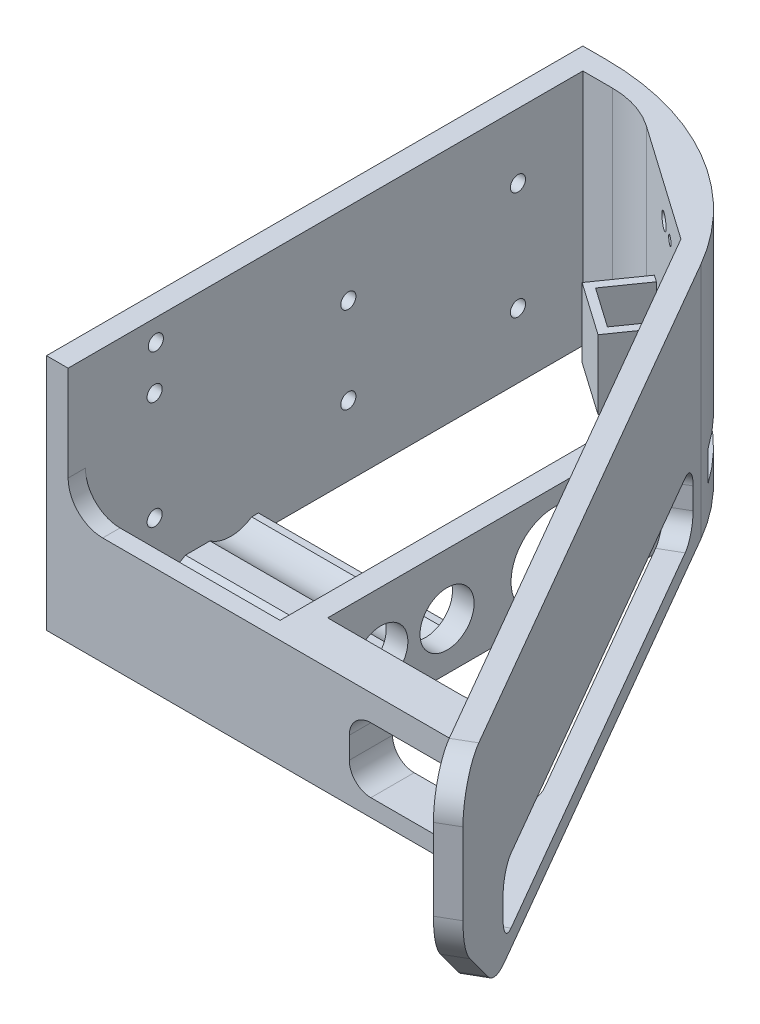
SolidWorks part; units mm, degrees
ref_plane "Front" through (0, 0, 0) normal (0, 0, 1) x (1, 0, 0)
ref_plane "Top" through (0, 0, 0) normal (0, 1, 0) x (1, 0, 0)
ref_plane "Right" through (0, 0, 0) normal (1, 0, 0) x (0, 0, -1)
sketch "Sketch3" plane through (0, 0, 0) normal (0, 1, 0) x (1, 0, 0)
  line L0 (128.1699, -162.7147) -> (55, -35.9808)
  line L1 (0, 0) -> (40, 0)
  line L2 (0, 0) -> (0, -124)
  line L3 (0, -124) -> (5, -124)
  line L4 (5, -5) -> (5, -124)
  line L5 (40, 0) -> (132.5, -160.2147)
  line L6 (132.5, -160.2147) -> (128.1699, -162.7147)
  line L7 (5, -5) -> (18.123, -5)
  line L10 (50, -27.3205) -> (50, -124)
  line L11 (50, -124) -> (55, -124)
  line L12 (55, -35.9808) -> (55, -124)
  line L13 (18.123, -5) -> (50, -27.3205)
  dimension "D1" = 5
  dimension "D2" = 5
  dimension "D3" = 5
  dimension "D4" = 120
  dimension "D5" = 124
  dimension "D6" = 185
  dimension "D7" = 40
  dimension "D8" = 5
  dimension "D9" = 45
  dimension "D10" = 145
extrude "Boss-Extrude3" add sketch "Sketch3" along normal blind 55 contours L2 L3 L4 L7 L13 L10 L11 L12 L0 L6 L5 L1
fillet "Fillet1" radius 60 1 edges at (40, 27.5, 0)
sketch "Sketch4" plane through (3.6131, 0, -5.16) normal (-0.5736, 0, 0.8192) x (0.8192, 0, 0.5736)
  line L1 (31.628, 30.3662) -> (46.628, 30.3662)
  line L2 (31.628, 30.3662) -> (31.628, 14.3662)
  line L3 (31.628, 14.3662) -> (46.628, 14.3662)
  line L4 (46.628, 30.3662) -> (46.628, 14.3662)
  line L5 (56.628, 55) -> (56.628, 0) construction
  dimension "D1" = 15
  dimension "D2" = 16
  dimension "D3" = 10
extrude "Boss-Extrude4" add sketch "Sketch4" along normal blind 12
sketch "Sketch5" plane through (3.6131, 0, -5.16) normal (-0.5736, 0, 0.8192) x (0.8192, 0, 0.5736)
  line L1 (19.128, 14.3662) -> (59.128, 14.3662)
  line L2 (19.128, 14.3662) -> (19.128, 7.3662)
  line L3 (19.128, 7.3662) -> (59.128, 7.3662)
  line L4 (59.128, 14.3662) -> (59.128, 7.3662)
  line L5 (39.128, 14.3662) -> (39.128, -8.9782) construction
  line L6 (31.628, 14.3662) -> (46.628, 14.3662) construction
  dimension "D1" = 40
  dimension "D2" = 7
extrude "Cut-Extrude1" cut sketch "Sketch5" against normal blind 14 and the other way blind 20
sketch "Sketch6" plane through (0, 30.3662, 0) normal (0, 1, 0) x (1, 0, 0)
  line L0 (31.0776, -14.0709) -> (25.2845, -22.3443)
  line L1 (25.2845, -22.3443) -> (34.459, -28.7684)
  line L2 (34.459, -28.7684) -> (40.2521, -20.4949)
  line L3 (40.2521, -20.4949) -> (31.0776, -14.0709)
  line L4 (34.9256, -31.4146) -> (41.8085, -21.5847) construction
  line L5 (22.6383, -22.8109) -> (29.5212, -12.9811) construction
  line L6 (34.9256, -31.4146) -> (22.6383, -22.8109) construction
  line L7 (41.8085, -21.5847) -> (29.5212, -12.9811) construction
  dimension "D1" = 1.9
  dimension "D2" = 1.9
  dimension "D3" = 1.9
extrude "Cut-Extrude2" cut sketch "Sketch6" against normal offset from surface (14 mm away) 2 up to face at (36.2555, 14.3662, 19.8332)
sketch "Sketch7" plane through (0, 16.3662, 0) normal (0, 1, 0) x (1, 0, 0)
  line L0 (31.0776, -14.0709) -> (34.459, -28.7684) construction
  line L1 (34.459, -28.7684) -> (25.2845, -22.3443) construction
  circle A0 centre (32.7683, -21.4196) radius 2
  dimension "D1" = 4
extrude "Cut-Extrude3" cut sketch "Sketch7" against normal blind 2
sketch "Sketch8" plane through (0, 55, 0) normal (0, 1, 0) x (1, 0, 0)
  line L0 (55, -35.9808) -> (50, -27.3205)
  line L1 (50, -27.3205) -> (50, -124)
  line L2 (50, -124) -> (55, -124)
  line L3 (55, -124) -> (55, -35.9808)
extrude "Cut-Extrude4" cut sketch "Sketch8" against normal blind 30
sketch "Sketch9" plane through (50, 0, 0) normal (-1, 0, 0) x (0, 0, 1)
  line L0 (27.3205, 0) -> (124, 0) construction
  circle A0 centre (61.5987, 11) radius 10
  circle A1 centre (86.3851, 11) radius 6.25
  circle A2 centre (101.7, 11) radius 6.25
  dimension "D1" = 12.5
  dimension "D2" = 12.5
  dimension "D3" = 20
  dimension "D4" = 11
extrude "Cut-Extrude5" cut sketch "Sketch9" against normal up to surface (5 mm away) up to face at (55, 12.5, 79.9904)
sketch "Sketch10" plane through (30, 0, -17.3205) normal (0.866, 0, -0.5) x (-0.5, 0, -0.866)
  line L0 (-54.641, 0) -> (-205, 0) construction
  line L1 (-179.641, 4) -> (-59.641, 4)
  line L2 (-179.641, 4) -> (-179.641, 19)
  line L3 (-179.641, 19) -> (-59.641, 19)
  line L4 (-59.641, 4) -> (-59.641, 19)
  line L5 (-54.641, 0) -> (-54.641, 55) construction
  dimension "D1" = 15
  dimension "D2" = 4
  dimension "D3" = 120
  dimension "D4" = 5
extrude "Cut-Extrude6" cut sketch "Sketch10" against normal up to surface (5 mm away) up to face at (77.7233, 26.6667, 75.3387)
sketch "Sketch11" plane through (50, 0, 0) normal (-1, 0, 0) x (0, 0, 1)
  line L0 (27.3205, 0) -> (124, 0) construction
  line L1 (124, 25) -> (120, 25)
  line L2 (124, 25) -> (124, 0)
  line L3 (124, 0) -> (120, 0)
  line L4 (120, 25) -> (120, 0)
  dimension "D1" = 4
extrude "Boss-Extrude5" add sketch "Sketch11" along normal up to surface (45 mm away) up to face at (5, 27.5, 64.5)
fillet "Fillet3" radius 20 1 edges at (18.123, 27.5, 5)
sketch "Sketch12" plane through (55, 0, 0) normal (1, 0, 0) x (0, 0, -1)
  line L1 (-124, 0) -> (-114, 0)
  line L2 (-124, 0) -> (-124, 4)
  line L3 (-124, 4) -> (-114, 4)
  line L4 (-114, 0) -> (-114, 4)
  dimension "D1" = 10
  dimension "D2" = 4
extrude "Boss-Extrude6" add sketch "Sketch12" along normal up to surface (50.8179 mm away) up to face at (85.4904, 11.5, 88.7917)
sketch "Sketch13" plane through (50, 0, 0) normal (-1, 0, 0) x (0, 0, 1)
  line L1 (80, 0) -> (120, 0)
  line L2 (80, 0) -> (80, 4)
  line L3 (80, 4) -> (120, 4)
  line L4 (120, 0) -> (120, 4)
  line L5 (120, 25) -> (120, 0) construction
  dimension "D1" = 4
  dimension "D2" = 40
extrude "Boss-Extrude7" add sketch "Sketch13" along normal up to surface (45 mm away) up to face at (5, 26.6667, 83)
fillet "Fillet4" radius 5 4 edges at (57.6554, 4, 35.5801) (117.6554, 4, 139.5032) (117.6554, 19, 139.5032) (57.6554, 19, 35.5801)
sketch "Sketch14" plane through (50, 0, 0) normal (-1, 0, 0) x (0, 0, 1)
  arc A0 (94.0426, 14.6896) -> (94.0426, 7.3104) centre (86.3851, 11) ccw
  arc A1 (94.0426, 7.3104) -> (94.0426, 14.6896) centre (101.7, 11) ccw
  circle A2 centre (101.7, 11) radius 6.25 construction
  circle A3 centre (86.3851, 11) radius 6.25 construction
  dimension "D1" = 17
  dimension "D2" = 17
extrude "Cut-Extrude7" cut sketch "Sketch14" along normal up to surface (45 mm away) up to face at (5, 21, 82.25)
sketch "Sketch15" plane through (0, 0, 0) normal (-1, 0, 0) x (0, 0, 1)
  line L0 (0, 55) -> (124, 55) construction
  line L1 (0, 55) -> (0, 0) construction
  line L2 (0, 0) -> (124, 0) construction
  line L3 (124, 55) -> (124, 0) construction
  circle A0 centre (104, 40) radius 1.75
  circle A1 centre (104, 15) radius 1.75
  circle A2 centre (20, 15) radius 1.75
  circle A3 centre (20, 40) radius 1.75
  dimension "D1" = 3.5
  dimension "D2" = 15
  dimension "D3" = 20
  dimension "D4" = 15
  dimension "D5" = 20
sketch "Sketch16" plane through (0, 0, 0) normal (-1, 0, 0) x (0, 0, 1)
  circle A0 centre (59.2085, 36.1358) radius 1.75
  circle A1 centre (59.2085, 16.1358) radius 1.75
  circle A2 centre (103.7183, 50.0137) radius 1.75
  dimension "D1" = 3.5
  dimension "D2" = 3.5
  dimension "D3" = 3.5
extrude "Cut-Extrude8" cut sketch "Sketch16" against normal up to surface (5 mm away) up to face at (5, 15.0833, 86.1809)
extrude "Cut-Extrude9" cut sketch "Sketch15" against normal blind 5
sketch "Sketch17" plane through (30, 0, -17.3205) normal (0.866, 0, -0.5) x (-0.5, 0, -0.866)
  line L0 (-49.2023, 7.3662) -> (-49.2023, 14.3662) construction
  line L1 (-2.6795, 55) -> (-54.641, 55) construction
  circle A0 centre (-34.2023, 47.5) radius 1.75
  circle A1 centre (-39.2023, 47.5) radius 1
  dimension "D1" = 2
  dimension "D2" = 3.5
  dimension "D3" = 5
  dimension "D4" = 10
  dimension "D5" = 7.5
extrude "Cut-Extrude10" cut sketch "Sketch17" against normal up to next
chamfer "Chamfer1" distance 20 angle 45 1 edges at (130.3349, 0, 161.4647)
fillet "Fillet6" radius 15 2 edges at (120.3349, 0, 144.1442) (130.3349, 20, 161.4647)
fillet "Fillet7" radius 10 1 edges at (130.3349, 55, 161.4647)
sketch "Sketch18" plane through (0, 4, 0) normal (0, 1, 0) x (1, 0, 0)
  line L0 (100.0444, -114) -> (55, -114) construction
  line L1 (55, -124) -> (70, -124)
  line L2 (55, -124) -> (55, -114)
  line L3 (55, -114) -> (70, -114)
  line L4 (70, -124) -> (70, -114)
  dimension "D1" = 15
extrude "Boss-Extrude8" add sketch "Sketch18" along normal up to vertex (21 mm away) up to point (55, 25, 35.9808)
sketch "Sketch19" plane through (70, 0, 0) normal (1, 0, 0) x (0, 0, -1)
  line L0 (-114, 25) -> (-114, 4) construction
  line L1 (-124, 25) -> (-114, 25)
  line L2 (-124, 25) -> (-124, 19)
  line L3 (-124, 19) -> (-114, 19)
  line L4 (-114, 25) -> (-114, 19)
  dimension "D1" = 6
extrude "Boss-Extrude9" add sketch "Sketch19" along normal up to surface (30.0444 mm away) up to face at (93.1064, 15.9906, 101.9831)
fillet "Fillet9" radius 5 2 edges at (70, 4, 119) (70, 19, 119)
fillet "Fillet10" radius 8 2 edges at (100.0444, 2, 114) (100.0444, 22, 114)
fillet "Fillet11" radius 8 1 edges at (5, 25, 122)
